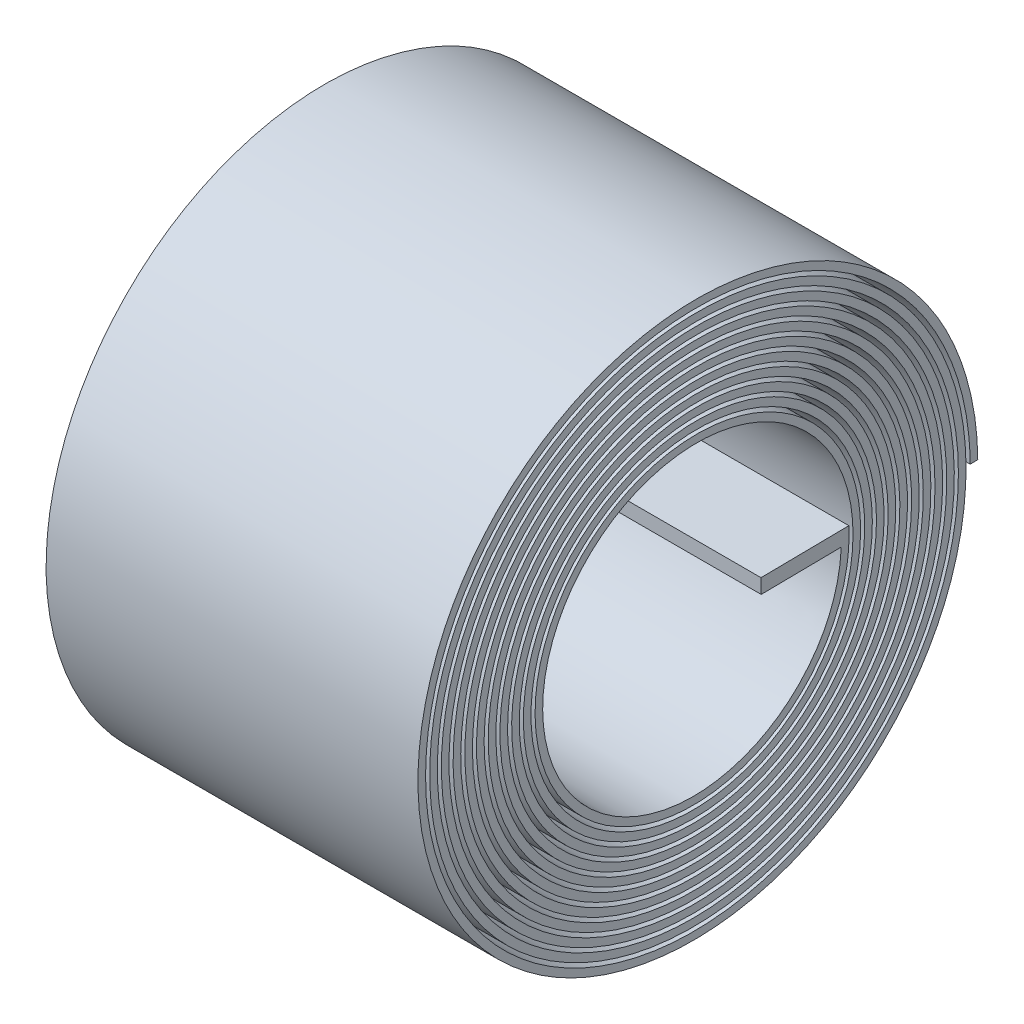
SolidWorks part; units mm, degrees
ref_plane "Front Plane" through (0, 0, 0) normal (0, 0, 1) x (1, 0, 0)
ref_plane "Top Plane" through (0, 0, 0) normal (0, 1, 0) x (1, 0, 0)
ref_plane "Right Plane" through (0, 0, 0) normal (1, 0, 0) x (0, 0, -1)
sketch "Sketch1" plane through (0, 0, 0) normal (1, 0, 0) x (0, 0, -1)
  circle A0 centre (0, 0) radius 2.5
  dimension "D1" = 5
curve "Helix/Spiral1"
sketch "Sketch2" plane through (0, 0, 0) normal (1, 0, 0) x (0, 0, -1)
  line L0 (2.5, 0) -> (2.63, 0.0017)
  line L2 (4.7, 0) -> (4.83, 0.0009)
  spline S0 degree 3 poles (-439.0072, -897.1615) (-56.85, 58.0039) (7.9525, 8.6548) (1.9311, -1.6856) (1.5943, -2.015) (0.7951, -2.4552) (0.3338, -2.5653) (-0.5842, -2.5317) (-1.0395, -2.3879) (-1.8147, -1.8837) (-2.1335, -1.5239) (-2.5418, -0.6873) (-2.6308, -0.2117) (-2.5504, 0.722) (-2.381, 1.1787) (-1.8283, 1.9431) (-1.4457, 2.2498) (-0.5729, 2.6237) (-0.084, 2.6904) (0.863, 2.5615) (1.3196, 2.366) (2.0704, 1.7647) (2.3634, 1.3597) (2.7003, 0.4521) (2.7437, -0.0491) (2.5648, -1.0068) (2.3429, -1.4619) (1.693, -2.196) (1.2659, -2.4739) (0.3252, -2.7713) (-0.1872, -2.7902) (-1.153, -2.5601) (-1.605, -2.3113) (-2.3194, -1.6131) (-2.5808, -1.1646) (-2.8362, -0.1923) (-2.8297, 0.33) (-2.5471, 1.3011) (-2.2713, 1.7484) (-1.5251, 2.4402) (-1.0557, 2.6836) (-0.0539, 2.8946) (0.4771, 2.8618) (1.4506, 2.5256) (1.8918, 2.2227) (2.5579, 1.4291) (2.7818, 0.9395) (2.9461, -0.0898) (2.8861, -0.6281) (2.4955, -1.6011) (2.1653, -2.0344) (1.3251, -2.6719) (0.8161, -2.875) (-0.2384, -2.9904) (-0.7826, -2.9024) (-1.752, -2.4566) (-2.1759, -2.0993) (-2.7817, -1.2133) (-2.9626, -0.6859) (-3.027, 0.3916) (-2.9104, 0.9402) (-2.4087, 1.9029) (-2.0244, 2.3158) (-1.0939, 2.8869) (-0.549, 3.0443) (0.549, 3.0557) (1.1004, 2.9097) (2.0533, 2.3519) (2.4534, 1.9409) (2.9869, 0.9671) (3.1195, 0.4057) (3.0762, -0.71) (2.9002, -1.2628) (2.286, -2.2026) (1.8486, -2.5884) (0.833, -3.0814) (0.2563, -3.1879) (-0.8744, -3.088) (-1.4268, -2.8817) (-2.3503, -2.2111) (-2.72, -1.7476) (-3.1697, -0.692) (-3.249, -0.1012) (-3.091, 1.0416) (-2.854, 1.592) (-2.1271, 2.4958) (-1.6382, 2.8479) (-0.5442, 3.2515) (0.0593, 3.3024) (1.2112, 3.085) (1.7579, 2.8169) (2.6387, 2.034) (2.9715, 1.5203) (3.3263, 0.3901) (3.3478, -0.2248) (3.0696, -1.3826) (2.7703, -1.9239) (1.932, -2.7784) (1.3942, -3.0903) (0.23, -3.3937) (-0.3949, -3.3848) (-1.5554, -3.0447) (-2.0895, -2.714) (-2.9142, -1.8211) (-3.2038, -1.2601) (-3.4533, -0.0641) (-3.413, 0.5691) (-3.0101, 1.7291) (-2.6481, 2.2541) (-1.7015, 3.0458) (-1.1181, 3.3114) (0.107, 3.5047) (0.7471, 3.4321) (1.903, 2.9657) (2.4172, 2.5725) (3.1726, 1.5732) (3.4126, 0.9686) (3.5474, -0.283) (3.4419, -0.9282) (2.9114, -2.0767) (2.4871, -2.5783) (1.4366, -3.294) (0.8117, -3.5071) (-0.4635, -3.5812) (-1.1121, -3.4421) (-2.2495, -2.8471) (-2.7366, -2.3921) (-3.4095, -1.2918) (-3.5943, -0.648) (-3.6057, 0.648) (-3.4324, 1.2982) (-2.7728, 2.421) (-2.2874, 2.8918) (-1.139, 3.5186) (-0.4775, 3.6737) (0.8359, 3.6206) (1.486, 3.4125) (2.5905, 2.6884) (3.0432, 2.1732) (3.6209, 0.9787) (3.7449, 0.3009) (3.6257, -1.0268) (3.3825, -1.6749) (2.5939, -2.7574) (2.0496, -3.1903) (0.811, -3.7157) (0.1184, -3.8075) (-1.2202, -3.6206) (-1.8644, -3.342) (-2.9213, -2.4894) (-3.3324, -1.9167) (-3.8027, -0.6363) (-3.8611, 0.0695) (-3.6051, 1.4156) (-3.2909, 2.0539) (-2.3751, 3.0814) (-1.7747, 3.4691) (-0.455, 3.8814) (0.2624, 3.9054) (1.6123, 3.579) (2.2428, 3.2292) (3.2373, 2.2509) (3.5998, 1.6239) (3.9513, 0.2676) (3.9398, -0.4598) (3.5423, -1.8098) (3.1567, -2.4305) (2.1171, -3.3882) (1.4645, -3.7239) (0.0743, -4.0121) (-0.6612, -3.9642) (-2.0076, -3.4946) (-2.6165, -3.0735) (-3.5338, -1.9738) (-3.8409, -1.2967) (-4.0633, 0.1242) (-3.9781, 0.8661) (-3.436, 2.2049) (-2.9796, 2.8) (-1.8213, 3.6733) (-1.121, 3.9503) (0.3277, 4.1045) (1.0739, 3.9814) (2.4013, 3.3663) (2.9806, 2.875) (3.8063, 1.6598) (4.0516, 0.9376) (4.1354, -0.5354) (3.9738, -1.2841) (3.2855, -2.5961) (2.7598, -3.1575) (1.4896, -3.9322) (0.7469, -4.1443) (-0.7469, -4.1557) (-1.4961, -3.955) (-2.7886, -3.1936) (-3.3302, -2.634) (-4.0504, -1.311) (-4.2279, -0.5494) (-4.1651, 0.9618) (-3.9249, 1.7093) (-3.0907, 2.9783) (-2.4979, 3.4981) (-1.1243, 4.1604) (-0.3455, 4.302) (1.1793, 4.1633) (1.9231, 3.8832) (3.1646, 2.9767) (3.6605, 2.3515) (4.2617, 0.93) (4.3661, 0.1356) (4.1501, -1.3989) (3.8299, -2.1368) (2.8518, -3.3467) (2.1952, -3.8169) (0.7284, -4.3539) (-0.0797, -4.4199) (-1.62, -4.1252) (-2.3499, -3.7649) (-3.5241, -2.7161) (-3.9667, -2.0291) (-4.4364, -0.52) (-4.4629, 0.3) (-4.0885, 1.842) (-3.6881, 2.5617) (-2.5698, 3.6962) (-1.8535, 4.1092) (-0.3052, 4.5089) (0.5248, 4.4949) (2.0642, 4.0398) (2.7716, 3.5994) (3.8622, 2.4131) (4.244, 1.6688) (4.5708, 0.0845) (4.5154, -0.7533) (3.9791, -2.2861) (3.499, -2.9788) (2.2462, -4.0217) (1.4753, -4.3704) (0.2627, -4.559) (-0.1504, -4.567) (-0.9645, -4.4723) (-1.3656, -4.3697) (-2.1264, -4.0607) (-2.4862, -3.8544) (-3.1383, -3.3528) (-3.4306, -3.0574) (-3.9263, -2.3988) (-4.1296, -2.0355) (-4.4321, -1.2671) (-4.5313, -0.862) (-4.6181, -0.0392) (-4.6057, 0.3785) (-4.4696, 1.1962) (-4.346, 1.5962) (-3.9961, 2.3494) (-3.7699, 2.7025) (-3.2308, 3.3363) (-2.9179, 3.6168) (-2.228, 4.0847) (-1.851, 4.272) (-1.0599, 4.5394) (-0.6458, 4.6195) (0.1896, 4.6662) (0.6108, 4.6329) (1.4299, 4.4548) (1.8277, 4.3101) (2.571, 3.9193) (2.9164, 3.6733) (3.5297, 3.0973) (3.7975, 2.7674) (4.2357, 2.0475) (4.4061, 1.6574) (9.2324, -15.3331) (-77.8687, -58.615) (-418.7177, 905.7456) knots -0.190695 -0.190695 -0.190695 -0.190695 0.007812 0.007812 0.015625 0.015625 0.023437 0.023437 0.03125 0.03125 0.039062 0.039062 0.046875 0.046875 0.054687 0.054687 0.0625 0.0625 0.070312 0.070312 0.078125 0.078125 0.085937 0.085937 0.09375 0.09375 0.101562 0.101562 0.109375 0.109375 0.117187 0.117187 0.125 0.125 0.132812 0.132812 0.140625 0.140625 0.148438 0.148438 0.15625 0.15625 0.164062 0.164062 0.171875 0.171875 0.179688 0.179688 0.1875 0.1875 0.195312 0.195312 0.203125 0.203125 0.210938 0.210938 0.21875 0.21875 0.226562 0.226562 0.234375 0.234375 0.242188 0.242188 0.25 0.25 0.257812 0.257812 0.265625 0.265625 0.273438 0.273438 0.28125 0.28125 0.289062 0.289062 0.296875 0.296875 0.304688 0.304688 0.3125 0.3125 0.320312 0.320312 0.328125 0.328125 0.335938 0.335938 0.34375 0.34375 0.351562 0.351562 0.359375 0.359375 0.367188 0.367188 0.375 0.375 0.382812 0.382812 0.390625 0.390625 0.398438 0.398438 0.40625 0.40625 0.414062 0.414062 0.421875 0.421875 0.429688 0.429688 0.4375 0.4375 0.445312 0.445312 0.453125 0.453125 0.460938 0.460938 0.46875 0.46875 0.476562 0.476562 0.484375 0.484375 0.492188 0.492188 0.5 0.5 0.507812 0.507812 0.515625 0.515625 0.523438 0.523438 0.53125 0.53125 0.539062 0.539062 0.546875 0.546875 0.554688 0.554688 0.5625 0.5625 0.570312 0.570312 0.578125 0.578125 0.585938 0.585938 0.59375 0.59375 0.601562 0.601562 0.609375 0.609375 0.617188 0.617188 0.625 0.625 0.632812 0.632812 0.640625 0.640625 0.648438 0.648438 0.65625 0.65625 0.664062 0.664062 0.671875 0.671875 0.679688 0.679688 0.6875 0.6875 0.695312 0.695312 0.703125 0.703125 0.710938 0.710938 0.71875 0.71875 0.726562 0.726562 0.734375 0.734375 0.742188 0.742188 0.75 0.75 0.757812 0.757812 0.765625 0.765625 0.773438 0.773438 0.78125 0.78125 0.789062 0.789062 0.796875 0.796875 0.804688 0.804688 0.8125 0.8125 0.820312 0.820312 0.828125 0.828125 0.835938 0.835938 0.84375 0.84375 0.851562 0.851562 0.859375 0.859375 0.867188 0.867188 0.875 0.875 0.882812 0.882812 0.890625 0.890625 0.898438 0.898438 0.90625 0.90625 0.914062 0.914062 0.921875 0.921875 0.929688 0.929688 0.933594 0.933594 0.9375 0.9375 0.941406 0.941406 0.945312 0.945312 0.949219 0.949219 0.953125 0.953125 0.957031 0.957031 0.960938 0.960938 0.964844 0.964844 0.96875 0.96875 0.972656 0.972656 0.976562 0.976562 0.980469 0.980469 0.984375 0.984375 0.988281 0.988281 0.992188 0.992188 0.996094 0.996094 1.155603 1.155603 1.155603 1.155603 only from (2.5, 0) to (4.7, 0) construction
  spline S1 degree 3 poles (2.5, 0) (2.5057, -0.45) (2.3871, -0.9025) (1.9311, -1.6856) (1.5943, -2.015) (0.7951, -2.4552) (0.3338, -2.5653) (-0.5842, -2.5317) (-1.0395, -2.3879) (-1.8147, -1.8837) (-2.1335, -1.5239) (-2.5418, -0.6873) (-2.6308, -0.2117) (-2.5504, 0.722) (-2.381, 1.1787) (-1.8283, 1.9431) (-1.4457, 2.2498) (-0.5729, 2.6237) (-0.084, 2.6904) (0.863, 2.5615) (1.3196, 2.366) (2.0704, 1.7647) (2.3634, 1.3597) (2.7003, 0.4521) (2.7437, -0.0491) (2.5648, -1.0068) (2.3429, -1.4619) (1.693, -2.196) (1.2659, -2.4739) (0.3252, -2.7713) (-0.1872, -2.7902) (-1.153, -2.5601) (-1.605, -2.3113) (-2.3194, -1.6131) (-2.5808, -1.1646) (-2.8362, -0.1923) (-2.8297, 0.33) (-2.5471, 1.3011) (-2.2713, 1.7484) (-1.5251, 2.4402) (-1.0557, 2.6836) (-0.0539, 2.8946) (0.4771, 2.8618) (1.4506, 2.5256) (1.8918, 2.2227) (2.5579, 1.4291) (2.7818, 0.9395) (2.9461, -0.0898) (2.8861, -0.6281) (2.4955, -1.6011) (2.1653, -2.0344) (1.3251, -2.6719) (0.8161, -2.875) (-0.2384, -2.9904) (-0.7826, -2.9024) (-1.752, -2.4566) (-2.1759, -2.0993) (-2.7817, -1.2133) (-2.9626, -0.6859) (-3.027, 0.3916) (-2.9104, 0.9402) (-2.4087, 1.9029) (-2.0244, 2.3158) (-1.0939, 2.8869) (-0.549, 3.0443) (0.549, 3.0557) (1.1004, 2.9097) (2.0533, 2.3519) (2.4534, 1.9409) (2.9869, 0.9671) (3.1195, 0.4057) (3.0762, -0.71) (2.9002, -1.2628) (2.286, -2.2026) (1.8486, -2.5884) (0.833, -3.0814) (0.2563, -3.1879) (-0.8744, -3.088) (-1.4268, -2.8817) (-2.3503, -2.2111) (-2.72, -1.7476) (-3.1697, -0.692) (-3.249, -0.1012) (-3.091, 1.0416) (-2.854, 1.592) (-2.1271, 2.4958) (-1.6382, 2.8479) (-0.5442, 3.2515) (0.0593, 3.3024) (1.2112, 3.085) (1.7579, 2.8169) (2.6387, 2.034) (2.9715, 1.5203) (3.3263, 0.3901) (3.3478, -0.2248) (3.0696, -1.3826) (2.7703, -1.9239) (1.932, -2.7784) (1.3942, -3.0903) (0.23, -3.3937) (-0.3949, -3.3848) (-1.5554, -3.0447) (-2.0895, -2.714) (-2.9142, -1.8211) (-3.2038, -1.2601) (-3.4533, -0.0641) (-3.413, 0.5691) (-3.0101, 1.7291) (-2.6481, 2.2541) (-1.7015, 3.0458) (-1.1181, 3.3114) (0.107, 3.5047) (0.7471, 3.4321) (1.903, 2.9657) (2.4172, 2.5725) (3.1726, 1.5732) (3.4126, 0.9686) (3.5474, -0.283) (3.4419, -0.9282) (2.9114, -2.0767) (2.4871, -2.5783) (1.4366, -3.294) (0.8117, -3.5071) (-0.4635, -3.5812) (-1.1121, -3.4421) (-2.2495, -2.8471) (-2.7366, -2.3921) (-3.4095, -1.2918) (-3.5943, -0.648) (-3.6057, 0.648) (-3.4324, 1.2982) (-2.7728, 2.421) (-2.2874, 2.8918) (-1.139, 3.5186) (-0.4775, 3.6737) (0.8359, 3.6206) (1.486, 3.4125) (2.5905, 2.6884) (3.0432, 2.1732) (3.6209, 0.9787) (3.7449, 0.3009) (3.6257, -1.0268) (3.3825, -1.6749) (2.5939, -2.7574) (2.0496, -3.1903) (0.811, -3.7157) (0.1184, -3.8075) (-1.2202, -3.6206) (-1.8644, -3.342) (-2.9213, -2.4894) (-3.3324, -1.9167) (-3.8027, -0.6363) (-3.8611, 0.0695) (-3.6051, 1.4156) (-3.2909, 2.0539) (-2.3751, 3.0814) (-1.7747, 3.4691) (-0.455, 3.8814) (0.2624, 3.9054) (1.6123, 3.579) (2.2428, 3.2292) (3.2373, 2.2509) (3.5998, 1.6239) (3.9513, 0.2676) (3.9398, -0.4598) (3.5423, -1.8098) (3.1567, -2.4305) (2.1171, -3.3882) (1.4645, -3.7239) (0.0743, -4.0121) (-0.6612, -3.9642) (-2.0076, -3.4946) (-2.6165, -3.0735) (-3.5338, -1.9738) (-3.8409, -1.2967) (-4.0633, 0.1242) (-3.9781, 0.8661) (-3.436, 2.2049) (-2.9796, 2.8) (-1.8213, 3.6733) (-1.121, 3.9503) (0.3277, 4.1045) (1.0739, 3.9814) (2.4013, 3.3663) (2.9806, 2.875) (3.8063, 1.6598) (4.0516, 0.9376) (4.1354, -0.5354) (3.9738, -1.2841) (3.2855, -2.5961) (2.7598, -3.1575) (1.4896, -3.9322) (0.7469, -4.1443) (-0.7469, -4.1557) (-1.4961, -3.955) (-2.7886, -3.1936) (-3.3302, -2.634) (-4.0504, -1.311) (-4.2279, -0.5494) (-4.1651, 0.9618) (-3.9249, 1.7093) (-3.0907, 2.9783) (-2.4979, 3.4981) (-1.1243, 4.1604) (-0.3455, 4.302) (1.1793, 4.1633) (1.9231, 3.8832) (3.1646, 2.9767) (3.6605, 2.3515) (4.2617, 0.93) (4.3661, 0.1356) (4.1501, -1.3989) (3.8299, -2.1368) (2.8518, -3.3467) (2.1952, -3.8169) (0.7284, -4.3539) (-0.0797, -4.4199) (-1.62, -4.1252) (-2.3499, -3.7649) (-3.5241, -2.7161) (-3.9667, -2.0291) (-4.4364, -0.52) (-4.4629, 0.3) (-4.0885, 1.842) (-3.6881, 2.5617) (-2.5698, 3.6962) (-1.8535, 4.1092) (-0.3052, 4.5089) (0.5248, 4.4949) (2.0642, 4.0398) (2.7716, 3.5994) (3.8622, 2.4131) (4.244, 1.6688) (4.5708, 0.0845) (4.5154, -0.7533) (3.9791, -2.2861) (3.499, -2.9788) (2.2462, -4.0217) (1.4753, -4.3704) (0.2627, -4.559) (-0.1504, -4.567) (-0.9645, -4.4723) (-1.3656, -4.3697) (-2.1264, -4.0607) (-2.4862, -3.8544) (-3.1383, -3.3528) (-3.4306, -3.0574) (-3.9263, -2.3988) (-4.1296, -2.0355) (-4.4321, -1.2671) (-4.5313, -0.862) (-4.6181, -0.0392) (-4.6057, 0.3785) (-4.4696, 1.1962) (-4.346, 1.5962) (-3.9961, 2.3494) (-3.7699, 2.7025) (-3.2308, 3.3363) (-2.9179, 3.6168) (-2.228, 4.0847) (-1.851, 4.272) (-1.0599, 4.5394) (-0.6458, 4.6195) (0.1896, 4.6662) (0.6108, 4.6329) (1.4299, 4.4548) (1.8277, 4.3101) (2.571, 3.9193) (2.9164, 3.6733) (3.5297, 3.0973) (3.7975, 2.7674) (4.2357, 2.0475) (4.4061, 1.6574) (4.6368, 0.8451) (4.6971, 0.423) (4.7, 0) knots 0 0 0 0 0.007812 0.007812 0.015625 0.015625 0.023437 0.023437 0.03125 0.03125 0.039062 0.039062 0.046875 0.046875 0.054687 0.054687 0.0625 0.0625 0.070312 0.070312 0.078125 0.078125 0.085937 0.085937 0.09375 0.09375 0.101562 0.101562 0.109375 0.109375 0.117187 0.117187 0.125 0.125 0.132812 0.132812 0.140625 0.140625 0.148438 0.148438 0.15625 0.15625 0.164062 0.164062 0.171875 0.171875 0.179688 0.179688 0.1875 0.1875 0.195312 0.195312 0.203125 0.203125 0.210938 0.210938 0.21875 0.21875 0.226562 0.226562 0.234375 0.234375 0.242188 0.242188 0.25 0.25 0.257812 0.257812 0.265625 0.265625 0.273438 0.273438 0.28125 0.28125 0.289062 0.289062 0.296875 0.296875 0.304688 0.304688 0.3125 0.3125 0.320312 0.320312 0.328125 0.328125 0.335938 0.335938 0.34375 0.34375 0.351562 0.351562 0.359375 0.359375 0.367188 0.367188 0.375 0.375 0.382812 0.382812 0.390625 0.390625 0.398438 0.398438 0.40625 0.40625 0.414062 0.414062 0.421875 0.421875 0.429688 0.429688 0.4375 0.4375 0.445312 0.445312 0.453125 0.453125 0.460938 0.460938 0.46875 0.46875 0.476562 0.476562 0.484375 0.484375 0.492188 0.492188 0.5 0.5 0.507812 0.507812 0.515625 0.515625 0.523438 0.523438 0.53125 0.53125 0.539062 0.539062 0.546875 0.546875 0.554688 0.554688 0.5625 0.5625 0.570312 0.570312 0.578125 0.578125 0.585938 0.585938 0.59375 0.59375 0.601562 0.601562 0.609375 0.609375 0.617188 0.617188 0.625 0.625 0.632812 0.632812 0.640625 0.640625 0.648438 0.648438 0.65625 0.65625 0.664062 0.664062 0.671875 0.671875 0.679688 0.679688 0.6875 0.6875 0.695312 0.695312 0.703125 0.703125 0.710938 0.710938 0.71875 0.71875 0.726562 0.726562 0.734375 0.734375 0.742188 0.742188 0.75 0.75 0.757812 0.757812 0.765625 0.765625 0.773438 0.773438 0.78125 0.78125 0.789062 0.789062 0.796875 0.796875 0.804688 0.804688 0.8125 0.8125 0.820312 0.820312 0.828125 0.828125 0.835938 0.835938 0.84375 0.84375 0.851562 0.851562 0.859375 0.859375 0.867188 0.867188 0.875 0.875 0.882812 0.882812 0.890625 0.890625 0.898438 0.898438 0.90625 0.90625 0.914062 0.914062 0.921875 0.921875 0.929688 0.929688 0.933594 0.933594 0.9375 0.9375 0.941406 0.941406 0.945312 0.945312 0.949219 0.949219 0.953125 0.953125 0.957031 0.957031 0.960938 0.960938 0.964844 0.964844 0.96875 0.96875 0.972656 0.972656 0.976562 0.976562 0.980469 0.980469 0.984375 0.984375 0.988281 0.988281 0.992188 0.992188 0.996094 0.996094 1 1 1 1
  spline S2 degree 1 poles (2.63, 0.0017) (4.83, 0.0009) knots 0 0 1 1 construction
  spline S3 degree 3 poles (2.63, 0.0017) (2.636, -0.4675) (2.3862, -1.4263) (1.3229, -2.4639) (-0.1332, -2.812) (-1.5699, -2.3583) (-2.5753, -1.2235) (-2.8559, 0.2763) (-2.322, 1.716) (-1.1163, 2.6822) (0.4241, 2.8924) (1.8622, 2.2768) (2.7848, 1.0016) (2.9212, -0.5761) (2.2228, -2.0081) (0.8794, -2.8824) (-0.7319, -2.9419) (-2.153, -2.1598) (-2.9746, -0.75) (-2.9542, 0.8911) (-2.0879, 2.2965) (-0.6137, 3.0609) (1.0533, 2.9579) (2.4381, 2.007) (3.1408, 0.4707) (2.9527, -1.2179) (1.9172, -2.5771) (0.3213, -3.214) (-1.3845, -2.9383) (-2.7131, -1.8185) (-3.28, -0.1658) (-2.9145, 1.5525) (-1.711, 2.8455) (-0.0047, 3.3383) (1.7215, 2.8812) (2.9738, 1.5948) (3.3886, -0.1618) (2.8383, -1.8909) (1.4701, -3.0974) (-0.3332, -3.4304) (-2.0602, -2.7856) (-3.2158, -1.337) (-3.4635, 0.5091) (-2.7229, 2.2287) (-1.1958, 3.3285) (0.689, 3.4874) (2.396, 2.6504) (3.435, 1.0468) (3.5019, -0.8725) (2.5679, -2.5615) (0.8901, -3.5347) (-1.059, -3.5067) (-2.7245, -2.4755) (-3.6272, -0.7261) (-3.5014, 1.248) (-2.3731, 2.8845) (-0.5552, 3.712) (1.4391, 3.486) (3.041, 2.2609) (3.7887, 0.3777) (3.4601, -1.6316) (2.1391, -3.1933) (0.1939, -3.8567) (-1.8249, -3.4236) (-3.3408, -2.0076) (-3.9157, -0.0045) (-3.3764, 2.0185) (-1.8668, 3.4831) (0.1904, 3.9653) (2.2119, 3.3183) (3.6194, 1.7167) (4.005, -0.39) (3.2492, -2.4043) (1.5578, -3.7493) (-0.594, -4.0346) (-2.5952, -3.1691) (-3.8722, -1.3902) (-4.0537, 0.8019) (-3.0781, 2.7839) (-1.2142, 3.9875) (1.013, 4.0619) (2.9699, 2.976) (4.0948, 1.0302) (4.0591, -1.2268) (2.8631, -3.1524) (0.8386, -4.1935) (-1.4427, -4.045) (-3.331, -2.7393) (-4.2832, -0.6397) (-4.0194, 1.6602) (-2.6048, 3.5048) (-0.4341, 4.3633) (1.8786, 3.982) (3.6735, 2.4597) (4.4334, 0.2221) (3.9327, -2.0972) (2.3043, -3.8362) (0.0043, -4.4931) (-2.3155, -3.8715) (-3.9923, -2.1388) (-4.5419, 0.2188) (-3.7982, 2.5328) (-1.9635, 4.1414) (0.4468, 4.5796) (2.7483, 3.7129) (4.2828, 1.7786) (4.6057, -0.6789) (3.6154, -2.9616) (1.5845, -4.4159) (-0.9146, -4.6199) (-3.1717, -3.5058) (-4.5401, -1.3817) (-4.622, 1.1534) (-3.3842, 3.3782) (-1.1704, 4.6549) (1.3945, 4.6116) (3.5803, 3.2507) (4.7599, 0.9511) (4.5886, -1.6374) (3.1055, -3.7774) (0.7243, -4.8543) (-1.8813, -4.5527) (-3.9687, -2.9486) (-4.9379, -0.4906) (-4.5039, 2.1256) (-2.7804, 4.1535) (-0.2503, 5.0105) (2.3695, 4.4404) (4.3314, 2.6064) (4.8242, 0.8582) (4.83, 0.0009) knots 0 0 0 0 0.007812 0.015625 0.023438 0.03125 0.039062 0.046875 0.054688 0.0625 0.070312 0.078125 0.085938 0.09375 0.101562 0.109375 0.117188 0.125 0.132812 0.140625 0.148438 0.15625 0.164062 0.171875 0.179688 0.1875 0.195312 0.203125 0.210938 0.21875 0.226562 0.234375 0.242188 0.25 0.257812 0.265625 0.273438 0.28125 0.289062 0.296875 0.304688 0.3125 0.320312 0.328125 0.335938 0.34375 0.351562 0.359375 0.367188 0.375 0.382812 0.390625 0.398438 0.40625 0.414062 0.421875 0.429688 0.4375 0.445312 0.453125 0.460938 0.46875 0.476562 0.484375 0.492188 0.5 0.507812 0.515625 0.523438 0.53125 0.539062 0.546875 0.554688 0.5625 0.570312 0.578125 0.585938 0.59375 0.601562 0.609375 0.617188 0.625 0.632812 0.640625 0.648438 0.65625 0.664062 0.671875 0.679688 0.6875 0.695312 0.703125 0.710938 0.71875 0.726562 0.734375 0.742188 0.75 0.757812 0.765625 0.773438 0.78125 0.789062 0.796875 0.804688 0.8125 0.820312 0.828125 0.835938 0.84375 0.851562 0.859375 0.867188 0.875 0.882812 0.890625 0.898438 0.90625 0.914062 0.921875 0.929688 0.9375 0.945312 0.953125 0.960938 0.96875 0.976562 0.984375 0.992188 1 1 1 1
  dimension "D1" = 0.13
extrude "Boss-Extrude1" add sketch "Sketch2" along normal mid plane 6.35
sketch "Sketch3" plane through (0, 0, 0) normal (1, 0, 0) x (0, 0, -1)
  circle A0 centre (0, 0) radius 4.83 construction
sketch "Sketch4" plane through (0, 0, 0) normal (1, 0, 0) x (0, 0, -1)
  line L0 (2.5, 0) -> (1.1301, -0.0174) construction
  line L5 (2.6316, -0.1233) -> (2.6284, 0.1266)
  line L6 (2.6284, 0.1266) -> (1.1285, 0.1075)
  line L7 (1.1285, 0.1075) -> (1.1317, -0.1424)
  line L8 (2.63, 0.0017) -> (2.5, 0) construction
  line L9 (2.6316, -0.1233) -> (1.1317, -0.1424)
  point P13 (2.63, 0.0017)
  dimension "D1" = 0.25
  dimension "D2" = 1.5
extrude "Boss-Extrude2" add sketch "Sketch4" along normal up to surface (3.175 mm away) and the other way up to surface (3.175 mm away) up to face at (3.175, 0.0005, -3.665) other way up to face at (-3.175, 0.0005, -3.665)
